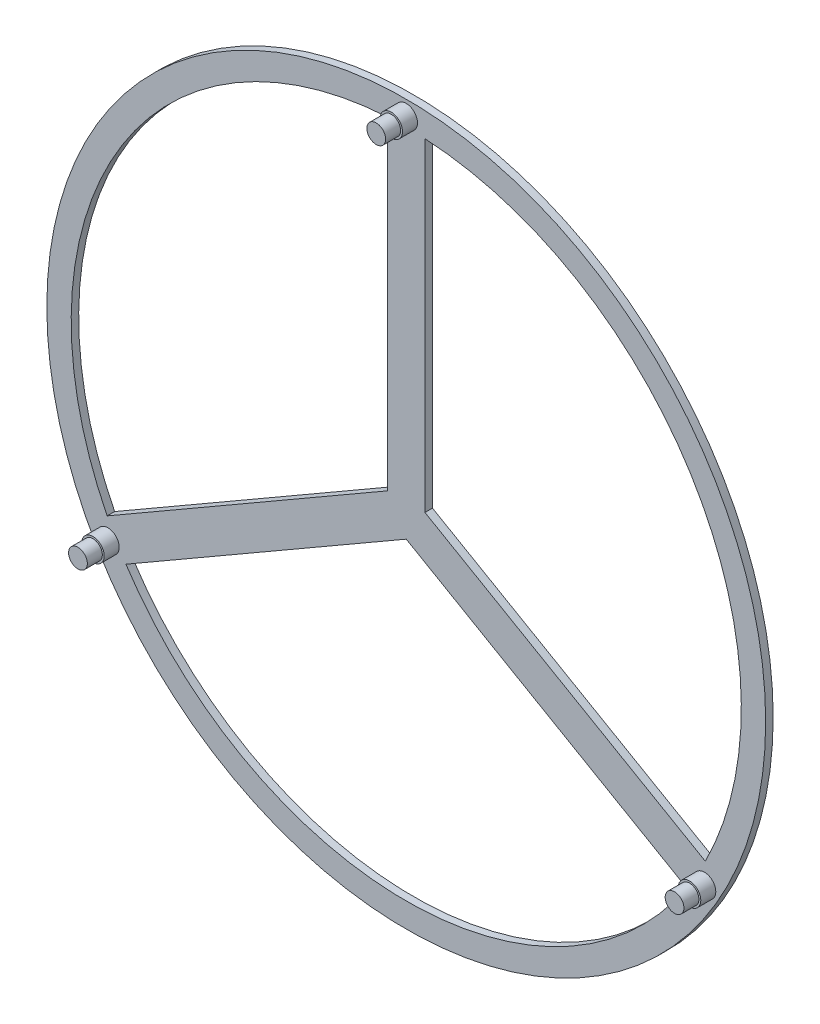
SolidWorks part; units mm, degrees
ref_plane "Front Plane" through (0, 0, 0) normal (0, 0, 1) x (1, 0, 0)
ref_plane "Top Plane" through (0, 0, 0) normal (0, 1, 0) x (1, 0, 0)
ref_plane "Right Plane" through (0, 0, 0) normal (1, 0, 0) x (0, 0, -1)
sketch "Sketch1" plane through (0, 0, 0) normal (0, 0, 1) x (1, 0, 0)
  line L1 (-6.0341, 1837.0131) -> (1584.8659, -918.5065)
  line L2 (-6.0341, 0) -> (1584.8659, -918.5065) construction
  line L4 (-6.0341, 0) -> (-6.0341, 1837.0131) construction
  line L9 (-6.0341, 0) -> (-1596.9341, -918.5065) construction
  line L10 (-56.0341, -86.6025) -> (1534.8659, -1005.1091) construction
  line L11 (93.9659, 0) -> (93.9659, 1837.0131) construction
  line L12 (-56.0341, 86.6025) -> (-1646.9341, -831.904) construction
  line L13 (43.9659, 86.6025) -> (1634.8659, -831.904) construction
  line L16 (1584.8659, -918.5065) -> (-1596.9341, -918.5065)
  line L17 (-6.0341, 1837.0131) -> (-1596.9341, -918.5065)
  line L18 (-106.0341, 0) -> (-106.0341, 1837.0131) construction
  line L19 (43.9659, -86.6025) -> (-1546.9341, -1005.1091) construction
  line L20 (-6.0341, -115.4701) -> (1489.1396, -978.709)
  line L21 (-6.0341, -115.4701) -> (-1501.2078, -978.709)
  line L22 (-1601.2078, -805.5039) -> (-106.0341, 57.735)
  line L23 (-106.0341, 57.735) -> (-106.0341, 1784.2129)
  line L24 (93.9659, 1784.2129) -> (93.9659, 57.735)
  line L25 (93.9659, 57.735) -> (1589.1396, -805.5039)
  circle A0 centre (1584.8659, -918.5065) radius 50
  circle A1 centre (-1596.9341, -918.5065) radius 50
  circle A2 centre (-6.0341, 1837.0131) radius 50
  circle A3 centre (-6.0341, 0) radius 1837.0131 construction
  circle A4 centre (-6.0341, 0) radius 1917.0131
  arc A5 (1589.1396, -805.5039) -> (93.9659, 1784.2129) centre (-6.0341, 0) ccw
  arc A6 (-1501.2078, -978.709) -> (1489.1396, -978.709) centre (-6.0341, 0) ccw
  circle A8 centre (-1596.9341, -918.5065) radius 60
  circle A9 centre (-6.0341, 1837.0131) radius 60
  circle A10 centre (1584.8659, -918.5065) radius 60
  circle A11 centre (-6.0341, 0) radius 1787.0131 construction
  arc A12 (-106.0341, 1784.2129) -> (-1601.2078, -805.5039) centre (-6.0341, 0) ccw
  point P10 (93.9659, 57.735)
  point P38 (2902.1767, 933.7589)
  point P40 (-6.0341, 0)
  dimension "D1" = 100
  dimension "D3" = 100
  dimension "D6" = 100
  dimension "D4" = 3181.8
  dimension "D5" = 80
  dimension "D9" = 10
  dimension "D2" = 50
  dimension "D7" = 100
  dimension "D8" = 100
extrude "Boss-Extrude1" add sketch "Sketch1" against normal blind 40 contours A10 L1 L25 L24 A9 L17 L23 L22 A8 L16 L21 L20 | L17 A9 L1 A2 | L17 A2 L1 | L1 A2 L17 | L1 A9 L17 A2 | A4 A12 L23 L17 A9 L1 L24 A5 L25 A10 L16 L20 A6 L21 A8 L22 | L1 A10 L16 A0 | L16 A10 L1 A0 | L16 A0 L1 | L1 A0 L16 | L17 A8 L16 A1 | L17 A1 L16 | L16 A1 L17 | L16 A8 L17 A1 region at (-6.0341, 1843.3793, 0) region at (-6.0341, 1805.1821, 0) region at (38.6885, 1811.1925, 0) region at (-6.0341, 1784.3473, 0) region at (-6.0341, 0, 0) region at (1614.0174, -868.0147, 0) region at (1539.256, -892.1736, 0) region at (-1551.3241, -892.1736, 0) region at (-1570.9038, -870.0266, 0) region at (1590.3792, -921.6896, 0) region at (1557.2995, -902.591, 0) region at (-1569.3676, -902.591, 0) region at (-1602.4474, -921.6896, 0) region at (-1868.8258, 0, 0)
extrude "Boss-Extrude2" add sketch "Sketch1<4>" along normal blind 160 contours A0 | A2 | A1
sketch "Sketch1<4>" plane through (0, 0, 0) normal (0, 0, 1) x (1, 0, 0) same geometry as "Sketch1"
extrude "Boss-Extrude3" add sketch "Sketch1<5>" along normal blind 80 and the other way blind 10 contours A9 | A10 | A8
sketch "Sketch1<5>" plane through (0, 0, 0) normal (0, 0, 1) x (1, 0, 0) same geometry as "Sketch1"
equation "\"HOLE_DIAM\"=100"
equation "\"D1@Sketch1\"=\"HOLE_DIAM\""
equation "\"D3@Sketch1\"=\"HOLE_DIAM\""
equation "\"D6@Sketch1\"=\"HOLE_DIAM\""
equation "\"D\"=3181.8"
equation "\"D4@Sketch1\"=\"D\""
